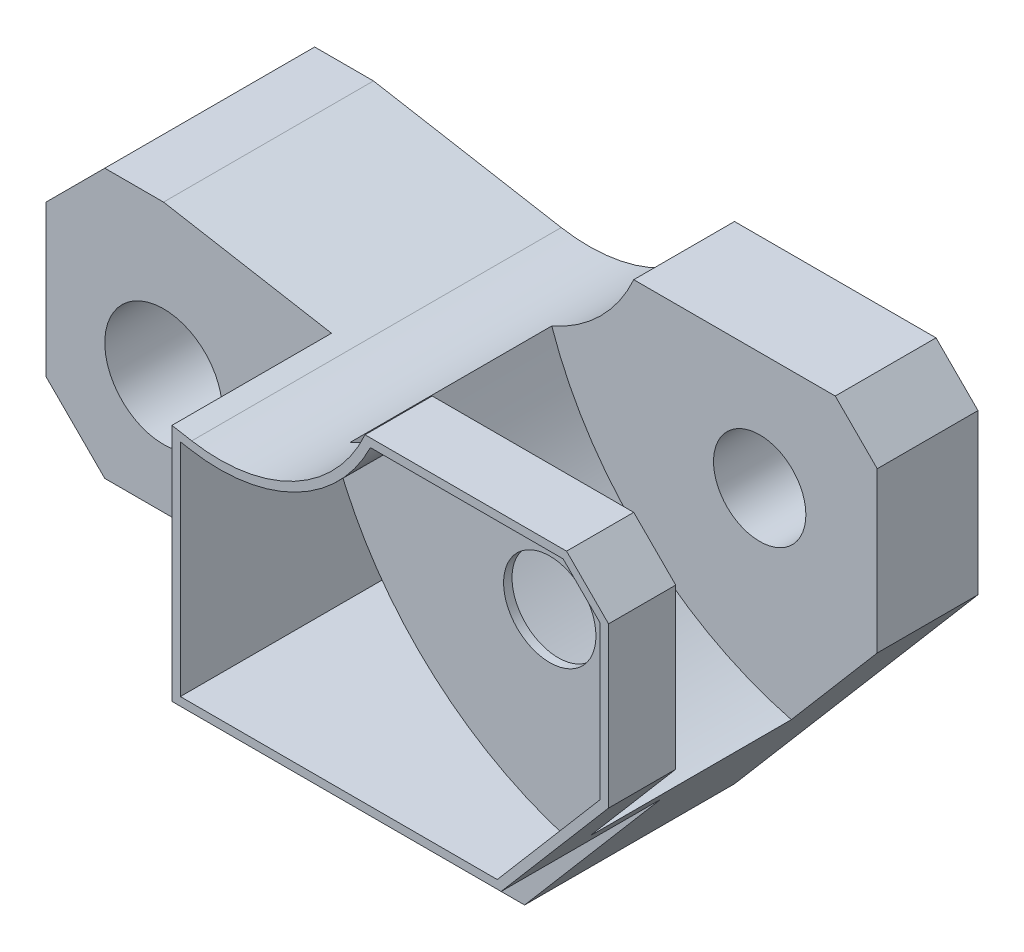
SolidWorks part; units mm, degrees
material "AISI 1020"
ref_plane "Plan de face" through (0, 0, 0) normal (0, 0, 1) x (1, 0, 0)
ref_plane "Plan de dessus" through (0, 0, 0) normal (0, 1, 0) x (1, 0, 0)
ref_plane "Plan de droite" through (0, 0, 0) normal (1, 0, 0) x (0, 0, -1)
sketch "Esquisse1" plane through (0, 0, 0) normal (0, 0, 1) x (1, 0, 0)
  line L0 (0, 0) -> (29, 34)
  line L1 (29, 34) -> (29, 53)
  line L2 (24, 58) -> (0, 58)
  line L3 (0, 0) -> (-5.703, 0)
  line L4 (-50, 19) -> (-17.4245, 19)
  line L5 (-57, 26) -> (-57, 44)
  line L6 (-50, 51) -> (-43, 51)
  line L7 (-43, 51) -> (-20.6386, 47.0571)
  line L8 (-42.6165, 0) -> (-43, 0) construction
  line L9 (-43, 0) -> (-43, 89.6438) construction
  line L10 (-94.4879, 33) -> (3.1136, 33) construction
  line L11 (-57, 44) -> (-50, 51)
  line L12 (-50, 19) -> (-57, 26)
  line L13 (29, 53) -> (24, 58)
  line L14 (-23, 47.4735) -> (-23, 19)
  line L15 (16.2059, 19) -> (-17.4245, 19)
  line L16 (23.5858, 57) -> (0.6361, 57)
  line L17 (28, 52.5858) -> (23.5858, 57)
  line L18 (28, 34.3685) -> (28, 52.5858)
  line L19 (15.7445, 20) -> (28, 34.3685)
  line L21 (-22, 20) -> (-17.4245, 20)
  line L26 (-43.0875, 50) -> (-43, 49.9846)
  line L27 (-22, 46.2817) -> (-22, 20)
  line L28 (-22, 46.2817) -> (-20.8123, 46.0723)
  line L29 (15.7445, 20) -> (-17.4245, 20)
  line L30 (-43.0875, 50) -> (-20.8123, 46.0723) construction
  line L31 (-49.5858, 50) -> (-43.0875, 50) construction
  line L32 (-56, 43.5858) -> (-49.5858, 50) construction
  line L33 (-56, 26.4142) -> (-56, 43.5858) construction
  line L34 (-49.5858, 20) -> (-56, 26.4142) construction
  line L35 (-49.5858, 20) -> (-17.4245, 20) construction
  line L36 (-22, 47.4735) -> (-22, 19) construction
  line L37 (-0.4614, 1) -> (-5.2417, 1) construction
  line L39 (-0.4614, 1) -> (28, 34.3685) construction
  line L40 (16.2059, 20) -> (-17.4245, 20) construction
  arc A0 (-12.4788, 14.7353) -> (-5.703, 0) centre (16.2059, 19) ccw
  arc A1 (-12.4788, 14.7353) -> (-17.4245, 19) centre (-17.4245, 14) ccw
  arc A2 (-20.6386, 47.0571) -> (0, 58) centre (-17.3393, 65.7684) ccw
  circle A3 centre (-43, 33) radius 7
  arc A4 (-9.7631, 48.3443) -> (18.7647, 22) centre (29, 61.7019) ccw
  circle A5 centre (15, 44) radius 5.5
  arc A6 (-20.8123, 46.0723) -> (0.6361, 57) centre (-17.3393, 65.7684) ccw
  arc A9 (-10.7085, 48.0185) -> (-10.6915, 47.9694) centre (29, 61.7019) ccw
  arc A10 (-10.3533, 47.0282) -> (16.9868, 21.4566) centre (29, 61.7019) ccw
  arc A12 (-10.7085, 48.0185) -> (18.5151, 21.0317) centre (29, 61.7019) ccw construction
  arc A13 (-11.4897, 14.8824) -> (-17.4245, 20) centre (-17.4245, 14) ccw construction
  arc A14 (-11.4897, 14.8824) -> (-5.2417, 1) centre (16.2059, 19) ccw construction
  point P3 (16.2059, 19)
  point P4 (29, 58)
  point P8 (-57, 19)
  point P13 (-57, 51)
  point P30 (18.7647, 22)
  dimension "D6" = 29
  dimension "D7" = 5
  dimension "D12" = 19
  dimension "D15" = 14
  dimension "D24" = 41
  dimension "D28" = 1
  dimension "11" = 11
  dimension "D1" = 29
  dimension "D2" = 58
  dimension "D3" = 24
  dimension "D4" = 29
  dimension "D5" = 19
  dimension "D8" = 86
  dimension "D9" = 32
  dimension "D10" = 10
  dimension "D11" = 14
  dimension "D13" = 14
  dimension "D14" = 14
  dimension "D16" = 7
  dimension "D17" = 45
  dimension "D18" = 7
  dimension "D19" = 45
  dimension "D20" = 5
  dimension "D21" = 45
  dimension "D22" = 52
  dimension "D23" = 36
  dimension "D25" = 0
  dimension "D26" = 14
  dimension "D27" = 14
  dimension "D29" = 1
extrude "Boss.-Extru.1" add sketch "Esquisse1" against normal blind 44 contours L7 A2 L2 L13 L1 L0 L3 A0 A1 L4 L12 L5 L11 L6 | A3
extrude "Enlèv. mat.-Extru.1" cut sketch "Esquisse1<4>" against normal blind 19 contours L14 L7 L6 L11 L5 L12 L4 A3 | A1 A0 L3 L0 L15 region at (-0.9101, 11.5361, 0) region at (-36.5, 19.4669, 0)
sketch "Esquisse1<4>" plane through (0, 0, 0) normal (0, 0, 1) x (1, 0, 0) same geometry as "Esquisse1"
extrude "Enlèv. mat.-Extru.2" cut sketch "Esquisse1<5>" against normal blind 24 from offset 8 contours A6 A4 L19 L18 L17 L16 A5 | A4 A6 L16 L17 L18 L19 L0 L1 L13 L2 A2 region at (18.3694, 22.652, 0) region at (1.4931, 31.9904, 0) offset against normal yes
sketch "Esquisse1<5>" plane through (0, 0, 0) normal (0, 0, 1) x (1, 0, 0) same geometry as "Esquisse1"
extrude "Enlèv. mat.-Extru.3" cut sketch "Esquisse1<7>" against normal through all contours A5 region at (15, 44, 0)
sketch "Esquisse1<7>" plane through (0, 0, 0) normal (0, 0, 1) x (1, 0, 0) same geometry as "Esquisse1"
extrude "Enlèv. mat.-Extru.4" cut sketch "Esquisse1<11>" against normal blind 32 contours A10 A6 L28 L27 L21 L29 L19 region at (-9.3893, 30.3966, 0)
sketch "Esquisse1<11>" plane through (0, 0, 0) normal (0, 0, 1) x (1, 0, 0) same geometry as "Esquisse1"
extrude "Enlèv. mat.-Extru.5" cut sketch "Esquisse1<12>" against normal blind 7 contours A6 A4 L19 L18 L17 L16 A5 | A6 A10 L19 A4 region at (1.4931, 31.9904, 0) region at (17.0517, 22.1214, 0)
sketch "Esquisse1<12>" plane through (0, 0, 0) normal (0, 0, 1) x (1, 0, 0) same geometry as "Esquisse1"
